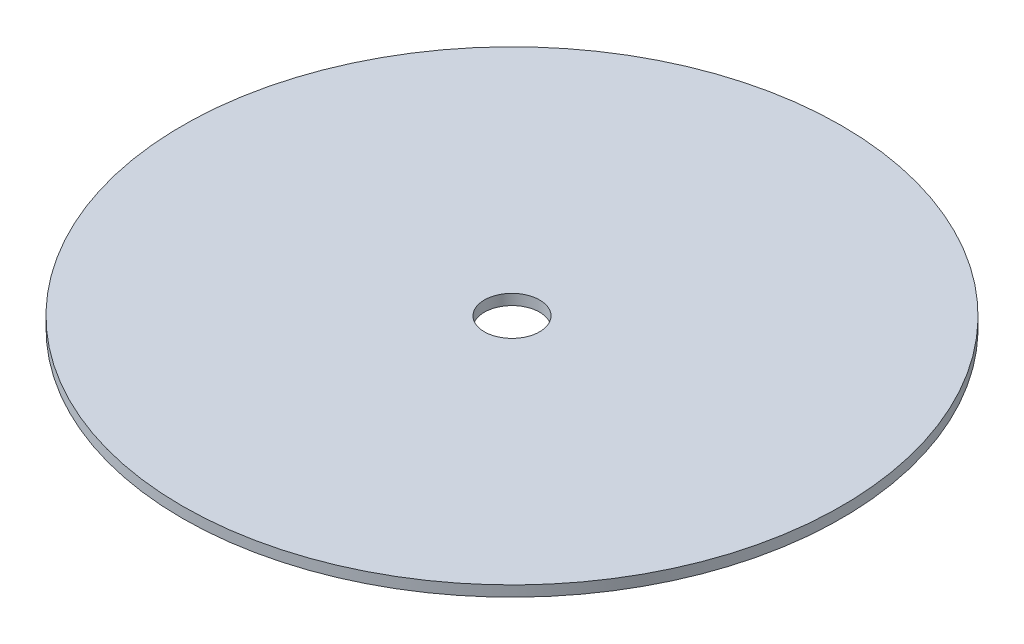
SolidWorks part; units mm, degrees
ref_plane "Front Plane" through (0, 0, 0) normal (0, 0, 1) x (1, 0, 0)
ref_plane "Top Plane" through (0, 0, 0) normal (0, 1, 0) x (1, 0, 0)
ref_plane "Right Plane" through (0, 0, 0) normal (1, 0, 0) x (0, 0, -1)
sketch "Sketch1" plane through (0, 0, 0) normal (0, 1, 0) x (1, 0, 0)
  circle A0 centre (0, 0) radius 98.425
  circle A2 centre (0, 0) radius 8.2489
  dimension "D1" = 196.85
  dimension "D2" = 16.4978
extrude "Boss-Extrude1" add sketch "Sketch1" along normal blind 3.175
